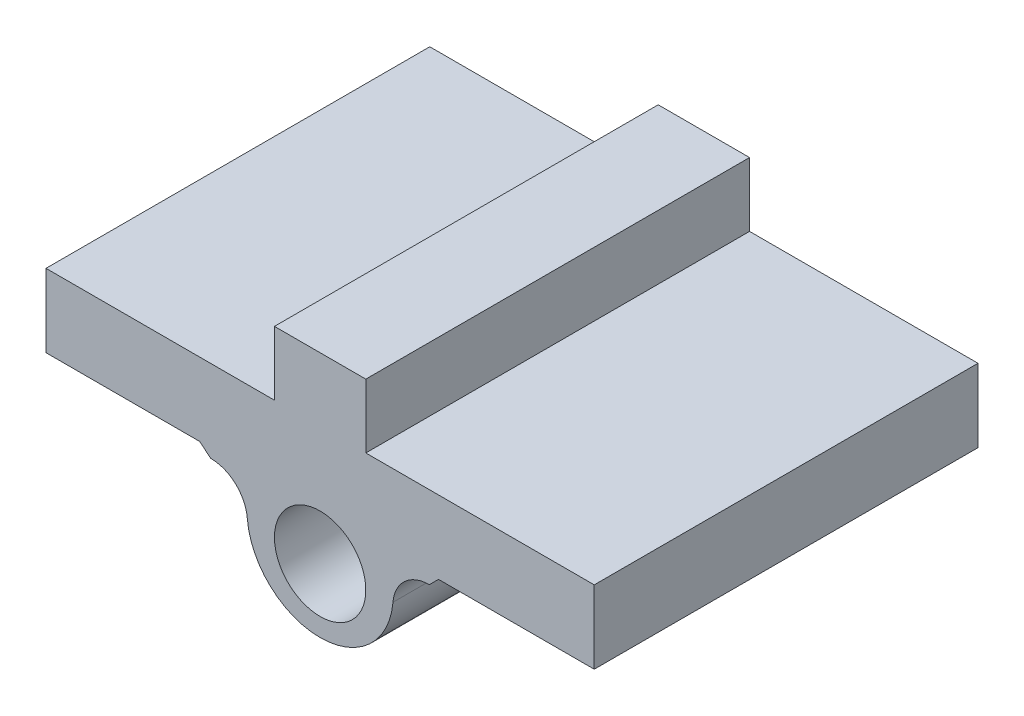
SolidWorks part; units mm, degrees
ref_plane "Front Plane" through (0, 0, 0) normal (0, 0, 1) x (1, 0, 0)
ref_plane "Top Plane" through (0, 0, 0) normal (0, 1, 0) x (1, 0, 0)
ref_plane "Right Plane" through (0, 0, 0) normal (1, 0, 0) x (0, 0, -1)
sketch "Sketch1" plane through (0, 0, 0) normal (0, 1, 0) x (1, 0, 0)
  line L1 (0, 0) -> (60, 0)
  line L2 (0, 0) -> (0, 42)
  line L3 (0, 42) -> (60, 42)
  line L4 (60, 0) -> (60, 42)
  dimension "D1" = 42
  dimension "D2" = 60
extrude "Boss-Extrude1" add sketch "Sketch1" along normal blind 8
sketch "Sketch3" plane through (0, 8, 0) normal (0, 1, 0) x (1, 0, 0)
  line L0 (60, 42) -> (0, 42) construction
  line L1 (25, 42) -> (35, 42)
  line L2 (25, 42) -> (25, 0)
  line L3 (25, 0) -> (35, 0)
  line L4 (35, 42) -> (35, 0)
  line L5 (0, 0) -> (60, 0) construction
  line L6 (0, 42) -> (0, 0) construction
  dimension "D1" = 10
  dimension "D2" = 25
extrude "Boss-Extrude5" add sketch "Sketch3" along normal blind 7
sketch "Sketch5" plane through (0, 0, 0) normal (0, -1, 0) x (1, 0, 0)
  line L0 (0, 0) -> (60, 0) construction
  line L1 (23, 0) -> (37, 0)
  line L2 (23, 0) -> (23, -42)
  line L3 (23, -42) -> (37, -42)
  line L4 (37, 0) -> (37, -42)
  line L5 (60, -42) -> (0, -42) construction
  line L6 (0, -42) -> (0, 0) construction
  dimension "D1" = 14
  dimension "D2" = 23
extrude "Boss-Extrude6" add sketch "Sketch5" along normal blind 11
sketch "Sketch6" plane through (0, 0, -42) normal (0, 0, -1) x (-1, 0, 0)
  line L0 (-23, -11) -> (-23, 0) construction
  line L1 (-37, -11) -> (-37, 0) construction
  line L2 (-23, -11) -> (-37, -11) construction
  circle A0 centre (-30, -5) radius 5
  dimension "D1" = 7
  dimension "D2" = 14
  dimension "D3" = 6
extrude "Cut-Extrude1" cut sketch "Sketch6" against normal through all
fillet "Fillet1" radius 7 2 edges at (23, -11, -21) (37, -11, -21)
fillet "Fillet2" radius 5 1 edges at (23, 0, -21)
fillet "Fillet3" radius 5 1 edges at (37, 0, -21)
sketch "Sketch8" plane through (0, 0, -42) normal (0, 0, -1) x (-1, 0, 0)
  line L0 (-41.9583, -1) -> (-42.9583, 0)
  line L1 (-60, 0) -> (-41.9583, 0) construction
  line L2 (-42.9583, 0) -> (-41.9583, 0)
  line L3 (-18.0417, -1) -> (-16.803, 0)
  line L4 (-18.0417, 0) -> (0, 0) construction
  line L5 (-16.803, 0) -> (-18.0417, 0)
  arc A0 (-18.0417, 0) -> (-23.0243, -4.5833) centre (-18.0417, -5) ccw construction
  arc A1 (-30, -11) -> (-23.0243, -4.5833) centre (-30, -4) ccw construction
  arc A2 (-36.9757, -4.5833) -> (-30, -11) centre (-30, -4) ccw construction
  arc A3 (-36.9757, -4.5833) -> (-41.9583, 0) centre (-41.9583, -5) ccw construction
  arc A4 (-18.0417, 0) -> (-23.0243, -4.5833) centre (-18.0417, -5) ccw
  arc A5 (-30, -11) -> (-23.0243, -4.5833) centre (-30, -4) ccw
  arc A6 (-36.9757, -4.5833) -> (-30, -11) centre (-30, -4) ccw
  arc A7 (-36.9757, -4.5833) -> (-41.9583, 0) centre (-41.9583, -5) ccw
  arc A8 (-18.0417, -1) -> (-22.0278, -4.6667) centre (-18.0417, -5) ccw
  arc A9 (-30, -12) -> (-22.0278, -4.6667) centre (-30, -4) ccw
  arc A10 (-37.9722, -4.6667) -> (-30, -12) centre (-30, -4) ccw
  arc A11 (-37.9722, -4.6667) -> (-41.9583, -1) centre (-41.9583, -5) ccw
  dimension "D1" = 1
extrude "Boss-Extrude7" add sketch "Sketch8" against normal up to surface (42 mm away) up to face at (25, -5, 0)
